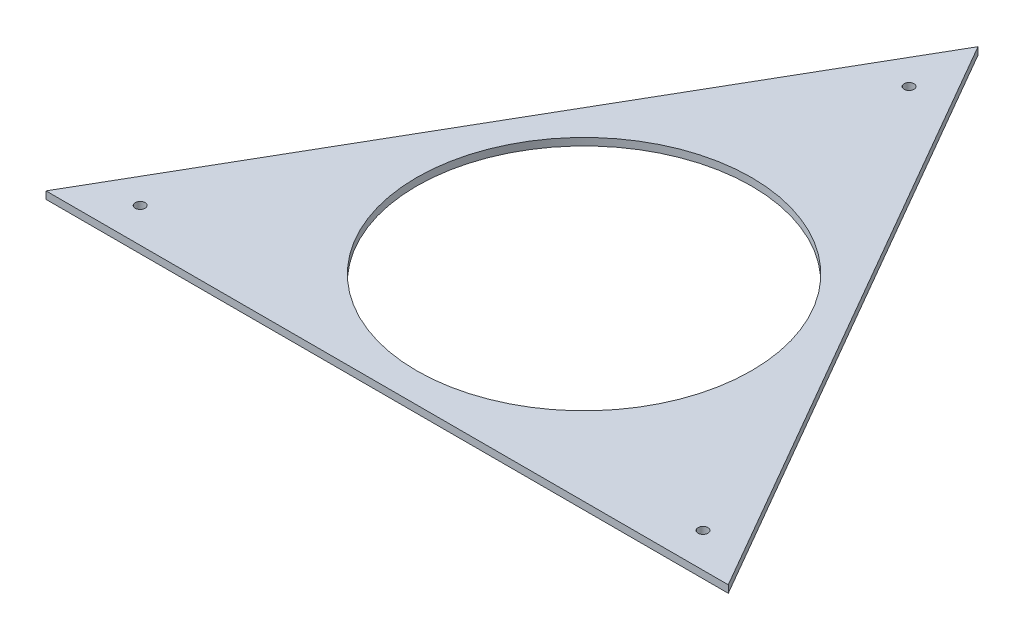
SolidWorks part; units mm, degrees
ref_plane "Front Plane" through (0, 0, 0) normal (0, 0, 1) x (1, 0, 0)
ref_plane "Top Plane" through (0, 0, 0) normal (0, 1, 0) x (1, 0, 0)
ref_plane "Right Plane" through (0, 0, 0) normal (1, 0, 0) x (0, 0, -1)
sketch "Sketch1" plane through (0, 0, 0) normal (0, 1, 0) x (1, 0, 0)
  line L1 (0, 254) -> (-219.9705, -127)
  line L2 (-219.9705, -127) -> (219.9705, -127)
  line L3 (219.9705, -127) -> (0, 254)
  circle A0 centre (0, 0) radius 127 construction
  dimension "D1" = 254
extrude "Boss-Extrude1" add sketch "Sketch1" along normal blind 4.7625 contours L1 L2 L3
sketch "Sketch5" plane through (0, 0, 0) normal (0, 1, 0) x (1, 0, 0)
  circle A0 centre (0, 0) radius 107.95
extrude "Cut-Extrude3" cut sketch "Sketch5" against normal blind 4.7625 and the other way blind 4.7625
sketch "Sketch6" plane through (0, 0, 0) normal (0, 1, 0) x (1, 0, 0)
  line L2 (0, 254) -> (-219.9705, -127) construction
  line L8 (-219.9705, -127) -> (219.9705, -127) construction
  line L13 (219.9705, -127) -> (0, 254) construction
  circle A0 centre (-181.4756, -104.775) radius 3.175
  circle A1 centre (0, 209.55) radius 3.175
  dimension "D1" = 19.05
  dimension "D2" = 19.05
  dimension "D3" = 6.35
  dimension "D4" = 19.05
  dimension "D5" = 19.05
  dimension "D6" = 6.35
extrude "Cut-Extrude5" cut sketch "Sketch6" along normal blind 4.7625
mirror "Mirror1" about plane through (0, 0, 0) normal (1, 0, 0) of "Cut-Extrude5"
